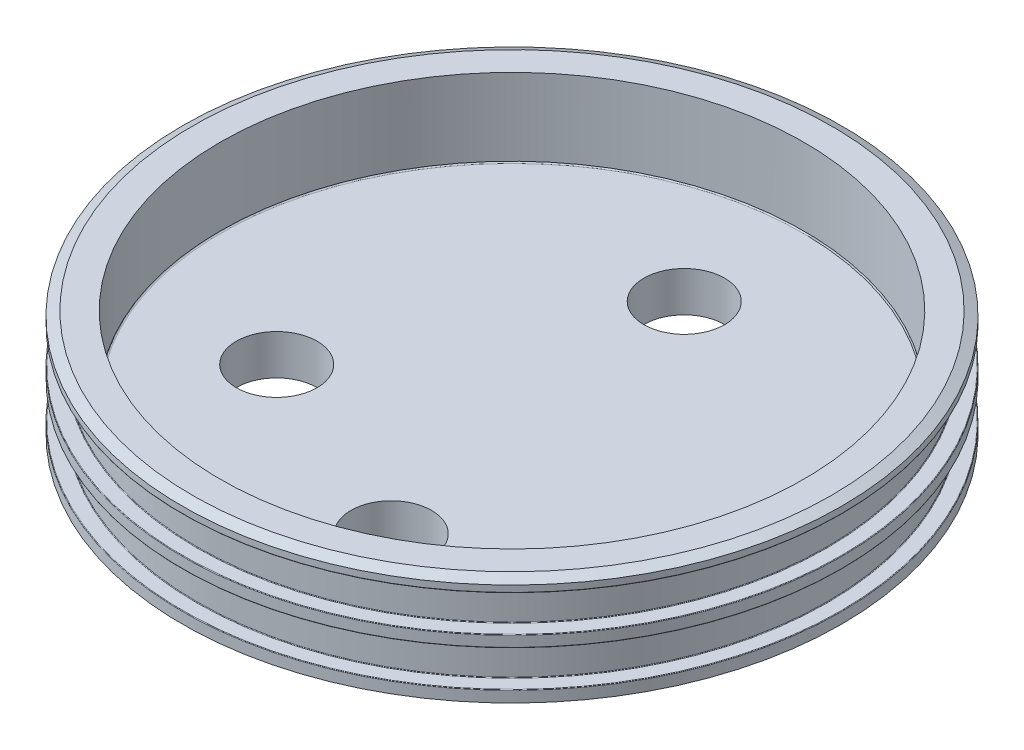
SolidWorks part; units mm, degrees
material "6061-T6 (SS)"
ref_plane "Front Plane" through (0, 0, 0) normal (0, 0, 1) x (1, 0, 0)
ref_plane "Top Plane" through (0, 0, 0) normal (0, 1, 0) x (1, 0, 0)
ref_plane "Right Plane" through (0, 0, 0) normal (1, 0, 0) x (0, 0, -1)
sketch "Sketch1" plane through (0, 0, 0) normal (0, 0, 1) x (1, 0, 0)
  line L0 (0, 48.1922) -> (0, -25.6743) construction
  line L1 (0, 0) -> (72.898, 0)
  line L2 (72.898, 0) -> (72.898, 2.54)
  line L3 (72.898, 2.54) -> (69.6468, 2.54)
  line L4 (69.6468, 2.54) -> (69.6468, 10.541)
  line L5 (69.6468, 10.541) -> (72.898, 10.541)
  line L6 (72.898, 10.541) -> (72.898, 13.081)
  line L7 (72.898, 13.081) -> (69.6468, 13.081)
  line L8 (64.5668, 23.622) -> (64.5668, 6.35)
  line L9 (64.5668, 6.35) -> (0, 6.35)
  line L10 (0, 6.35) -> (0, 0)
  line L11 (69.6468, 13.081) -> (69.6468, 21.082)
  line L12 (69.6468, 21.082) -> (72.898, 21.082)
  line L13 (72.898, 21.082) -> (72.898, 23.622)
  line L14 (72.898, 23.622) -> (64.5668, 23.622)
  dimension "D1" = 145.796
  dimension "D2" = 8.001
  dimension "D5" = 6.35
  dimension "D7" = 8.001
  dimension "D3" = 2.54
  dimension "D4" = 2.54
  dimension "D6" = 69.6468
  dimension "D8" = 5.08
revolve "Revolve1" add sketch "Sketch1" angle 360 about L0
sketch "Sketch6" plane through (0, 0, 0) normal (0, -1, 0) x (1, 0, 0)
  circle A0 centre (0, 0) radius 66.04
  dimension "D1" = 132.08
extrude "Boss-Extrude1" add sketch "Sketch6" along normal blind 2.54
fillet "CNC ID Fillet" radius 0.127 5 edges at (-69.6468, 10.541, 0) (-69.6468, 2.54, 0) (66.04, 0, 0) (-69.6468, 21.082, 0) (-69.6468, 13.081, 0)
fillet "CNC OD Fillet" radius 0.127 5 edges at (-72.898, 10.541, 0) (-72.898, 2.54, 0) (-72.898, 13.081, 0) (-72.898, 21.082, 0) (66.04, -2.54, 0)
chamfer "CNC Chamfers" distance 1.016 angle 65 1 edges at (-72.898, 23.622, 0) first distance on face at (-72.898, 21.209, 0)
fillet "CNC Bore Fillet" radius 0.254 1 edges at (-64.5668, 6.35, 0)
hole_wizard "Pipe Tap Drill for 1/2 Tap - Fill Valve" positions "Sketch13" profile "Sketch14" hole size "1/2" standard "ANSI Inch" end condition through all
sketch "Sketch13" plane through (0, -2.54, 0) normal (0, -1, 0) x (-1, 0, 0)
  point P4 (0, 38.1)
  dimension "D1" = 38.1
sketch "Sketch14" plane through (0, -2.54, -38.1) normal (1, 0, 0) x (0, 0, -1)
  line L0 (0, 0) -> (0, 26.162)
  line L1 (0, 26.162) -> (8.9281, 26.162)
  line L2 (8.9281, 26.162) -> (8.9281, 0)
  line L5 (8.9281, 0) -> (0, 0)
  line L11 (0, -6.35) -> (0, 107.95) construction
  dimension "Thru Hole Dia." = 17.8562
  dimension "Thru Hole Depth" = 26.162
hole_wizard "Pipe Tap Drill for 1/4 Tap - Solenoid Valve" positions "Sketch15" profile "Sketch16" hole size "1/2" standard "ANSI Inch" end condition through all
sketch "Sketch15" plane through (0, -2.54, 0) normal (0, -1, 0) x (-1, 0, 0)
  line L2 (-12.0892, -38.8003) -> (0, 0) construction
  line L3 (0, 0) -> (0, -38.8003) construction
  point P4 (-12.0892, -38.8003)
  dimension "D1" = 17.306
  dimension "D2" = 40.64
  dimension "D3" = 38.8003
sketch "Sketch16" plane through (12.0892, -2.54, 38.8003) normal (1, 0, 0) x (0, 0, -1)
  line L0 (0, 0) -> (0, 26.162)
  line L1 (0, 26.162) -> (8.9281, 26.162)
  line L2 (8.9281, 26.162) -> (8.9281, 0)
  line L5 (8.9281, 0) -> (0, 0)
  line L11 (0, -6.35) -> (0, 107.95) construction
  dimension "Thru Hole Dia." = 17.8562
  dimension "Thru Hole Depth" = 26.162
hole_wizard "Pipe Tap Drill for 1/2 Tap - Cryo Valve" positions "Sketch17" profile "Sketch18" hole size "1/2" standard "ANSI Inch" end condition through all
sketch "Sketch17" plane through (0, -2.54, 0) normal (0, -1, 0) x (-1, 0, 0)
  line L0 (32.9956, -19.05) -> (17.2813, -19.05) construction
  line L2 (32.9956, -19.05) -> (0, 0) construction
  point P4 (32.9956, -19.05)
  dimension "D1" = 30
  dimension "D2" = 38.1
sketch "Sketch18" plane through (-32.9956, -2.54, 19.05) normal (1, 0, 0) x (0, 0, -1)
  line L0 (0, 0) -> (0, 26.162)
  line L1 (0, 26.162) -> (8.9281, 26.162)
  line L2 (8.9281, 26.162) -> (8.9281, 0)
  line L5 (8.9281, 0) -> (0, 0)
  line L11 (0, -6.35) -> (0, 107.95) construction
  dimension "Thru Hole Dia." = 17.8562
  dimension "Thru Hole Depth" = 26.162
equation "\"D6@Sketch1\"=5.484/2"
